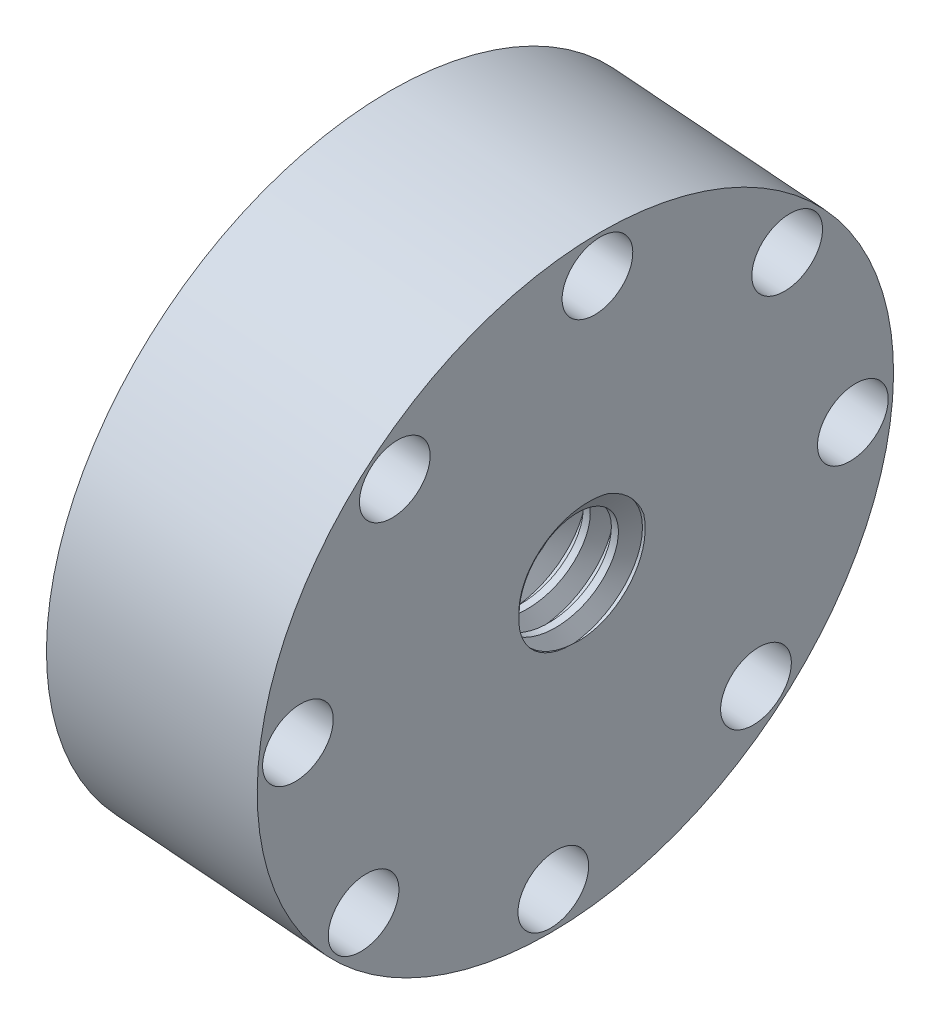
SolidWorks part; units mm, degrees
ref_plane "Front Plane" through (0, 0, 0) normal (0, 0, 1) x (1, 0, 0)
ref_plane "Top Plane" through (0, 0, 0) normal (0, 1, 0) x (1, 0, 0)
ref_plane "Right Plane" through (0, 0, 0) normal (1, 0, 0) x (0, 0, -1)
sketch "Sketch1" plane through (234.2789, -18.689, 0) normal (0.9968, -0.0795, 0) x (0, 0, -1)
  circle A1 centre (-43.1743, 8.5503) radius 14.2875
  dimension "D1" = 28.575
extrude "Boss-Extrude1" add sketch "Sketch1" against normal blind 9.525
sketch "Sketch2" plane through (234.2789, -18.689, 0) normal (0.9968, -0.0795, 0) x (0, 0, -1)
  circle A0 centre (-43.1743, 8.5503) radius 2.54
extrude "Cut-Extrude1" cut sketch "Sketch2" against normal blind 6.35
sketch "Sketch3" plane through (224.784, -17.9316, 0) normal (-0.9968, 0.0795, 0) x (0, 0, 1)
  circle A0 centre (43.1743, 21.0503) radius 1.5875
  circle A1 centre (43.1743, 8.5503) radius 14.2875 construction
  circle A2 centre (43.1743, 8.5503) radius 14.2875
  circle A3 centre (52.0131, 17.3892) radius 1.5875
  circle A4 centre (55.6743, 8.5503) radius 1.5875
  circle A5 centre (52.0131, -0.2885) radius 1.5875
  circle A6 centre (43.1743, -3.9497) radius 1.5875
  circle A7 centre (34.3354, -0.2885) radius 1.5875
  circle A8 centre (30.6743, 8.5503) radius 1.5875
  circle A9 centre (34.3354, 17.3892) radius 1.5875
  point P21 (43.1743, 8.5503)
  dimension "D1" = 3.175
  dimension "D3" = 12.5
  dimension "D2" = 8
extrude "Cut-Extrude2" cut sketch "Sketch3" against normal blind 10 contours A8 | A0 | A3 | A4 | A5 | A6 | A7 | A9 region at (226.458, 3.0521, 43.1743) region at (226.1668, -0.5975, 52.0131) region at (225.464, -9.4083, 55.6743) region at (224.7611, -18.2192, 52.0131) region at (224.47, -21.8687, 43.1743) region at (224.7611, -18.2192, 34.3354) region at (225.464, -9.4083, 30.6743)
sketch "Sketch4" plane through (234.2789, -18.689, 0) normal (0.9968, -0.0795, 0) x (0, 0, -1)
  line L0 (-57.4618, 8.5503) -> (-28.8868, 8.5503) construction
  circle A0 centre (-43.1743, 8.5503) radius 14.2875 construction
thread "Thread1" pitch 1.27 method cut profile "Thread Profile1" start angle 0, offset 0.9525, length 6.35, pitch 1.27, diameter 5.08
ref_plane "Plane1" through (235.9083, -10.2415, 45.7143) normal (-0.0795, -0.9968, 0) x (0, 0, 1)
sketch "Thread Profile1" plane through (235.9083, -10.2415, 45.7143) normal (-0.0795, -0.9968, 0) x (0, 0, 1)
  line L0 (0, 0) -> (0, 1.27) construction
  line L1 (0, 0) -> (0.6874, 0.3969)
  line L2 (0.6874, 0.3969) -> (0.6874, 0.5556)
  line L3 (0.6874, 0.5556) -> (0, 0.9525)
  line L4 (0.6874, 0.4762) -> (0, 0.4762) construction
  line L11 (0, 0) -> (0, 0.9525)
  point P2 (0, 0)
  dimension "Pitch" = 1.27
  dimension "Profile_Angle" = 60
  dimension "Profile_Land" = 0.1588
  dimension "Profile_Height" = 0.6874
